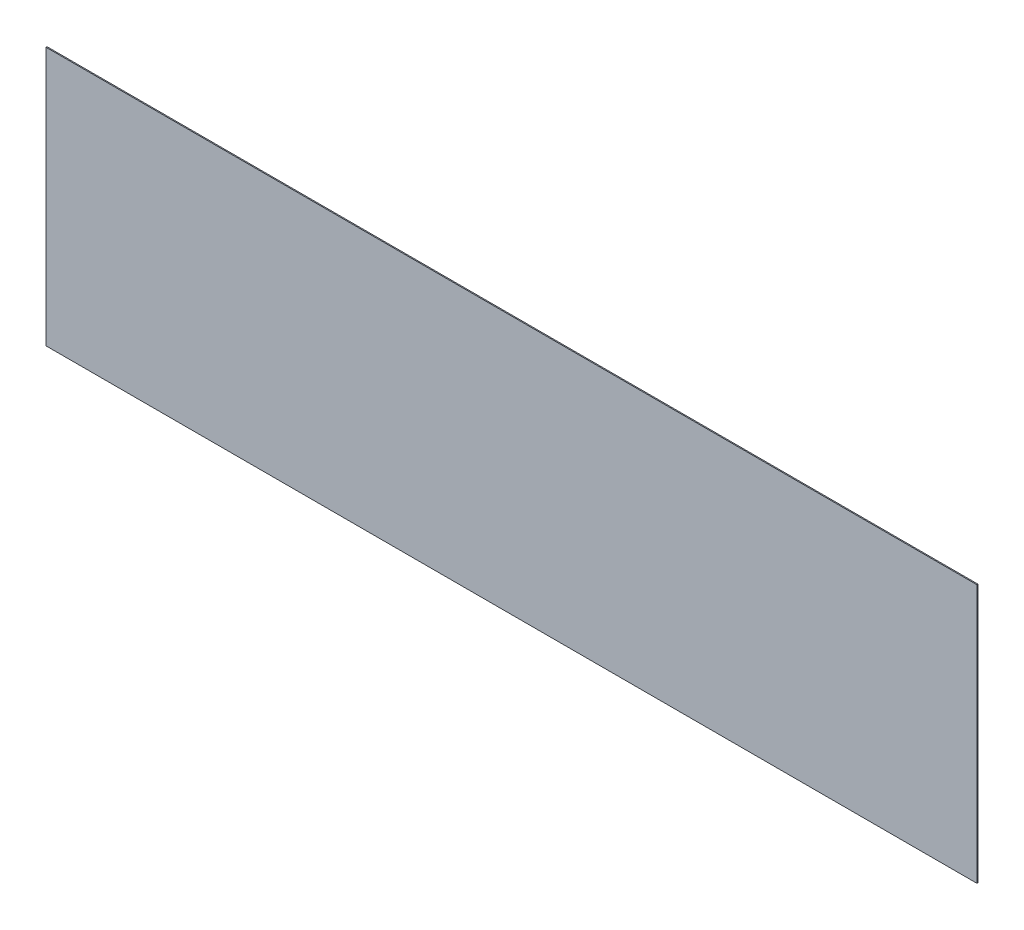
SolidWorks part; units mm, degrees
material "Balsa"
ref_plane "Front Plane" through (0, 0, 0) normal (0, 0, 1) x (1, 0, 0)
ref_plane "Top Plane" through (0, 0, 0) normal (0, 1, 0) x (1, 0, 0)
ref_plane "Right Plane" through (0, 0, 0) normal (1, 0, 0) x (0, 0, -1)
sketch "Sketch1" plane through (0, 0, 0) normal (0, 0, 1) x (1, 0, 0)
  line L1 (-900, -250) -> (900, -250)
  line L2 (-900, -250) -> (-900, 250)
  line L3 (-900, 250) -> (900, 250)
  line L4 (900, -250) -> (900, 250)
  line L5 (-900, -250) -> (900, 250) construction
  line L6 (-900, 250) -> (900, -250) construction
  point P0 (0, 0)
  dimension "D1" = 500
  dimension "D2" = 1800
base flange "Base-Flange1" sketch "Sketch1" thickness 2 reverse thickness direction no parameters "D1"=0.7366
sketch "Bend-Lines1" [suppressed] plane through (0, 0, 0) normal (0, 1, 0) x (1, 0, 0)
sketch "Bounding-Box1" [suppressed] plane through (0, 0, 0) normal (0, 1, 0) x (1, 0, 0)
sheet metal parameters "Sheet-Metal1" thickness 2 parameters "D1"=0.7366
flat pattern "Flat-Pattern1" [suppressed]
sketch "Bend-Lines2" plane through (0, 0, 0) normal (0, 1, 0) x (1, 0, 0)
sketch3d "Bounding-Box2" [suppressed]
  line L0 (-900, -250, 0) -> (900, -250, 0) construction
  line L1 (-900, 250, 0) -> (900, 250, 0) construction
  line L2 (-900, -250, 0) -> (-900, 250, 0) construction
  line L3 (900, -250, 0) -> (900, 250, 0) construction
